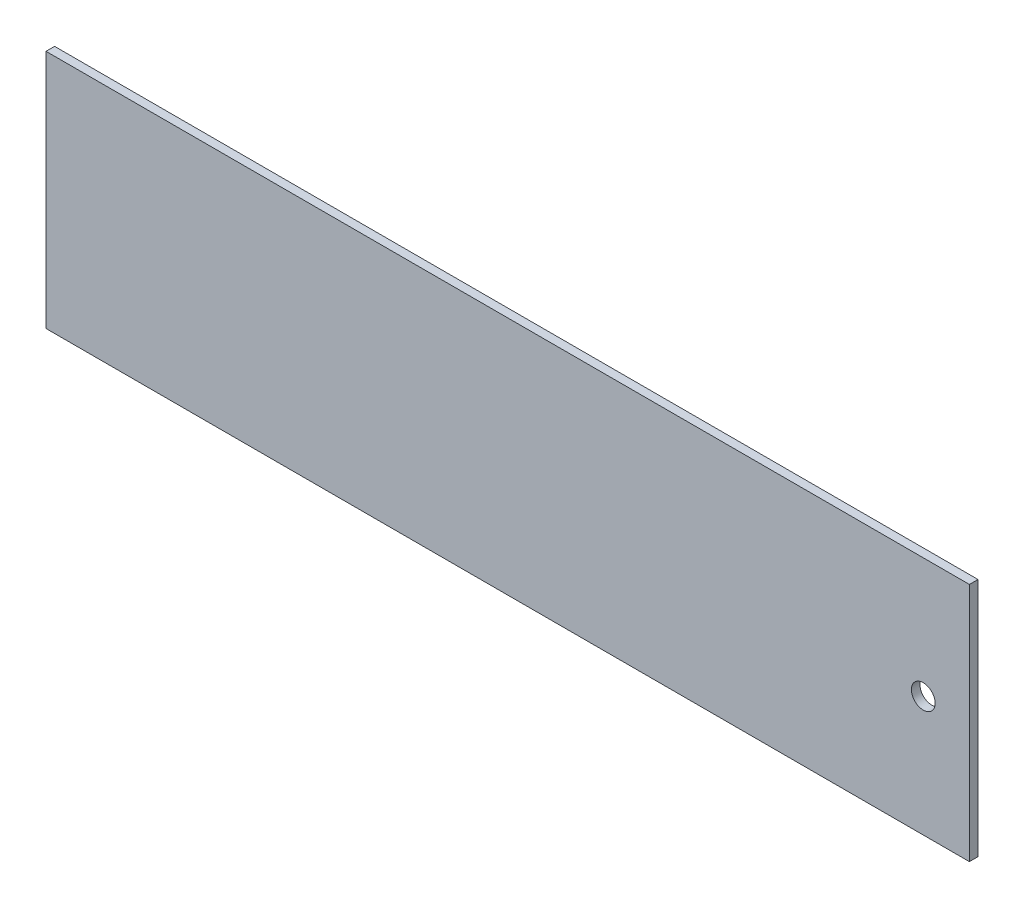
SolidWorks part; units mm, degrees
ref_plane "Front Plane" through (0, 0, 0) normal (0, 0, 1) x (1, 0, 0)
ref_plane "Top Plane" through (0, 0, 0) normal (0, 1, 0) x (1, 0, 0)
ref_plane "Right Plane" through (0, 0, 0) normal (1, 0, 0) x (0, 0, -1)
sketch "Sketch2" plane through (0, 0, 0) normal (0, 0, 1) x (1, 0, 0)
  line L1 (0, 0) -> (-254, 0)
  line L2 (0, 0) -> (0, 66.04)
  line L3 (0, 66.04) -> (-254, 66.04)
  line L4 (-254, 0) -> (-254, 66.04)
  dimension "D1" = 66.04
  dimension "D2" = 254
extrude "Boss-Extrude1" add sketch "Sketch2" along normal blind 2.3622
sketch "Sketch3" plane through (0, 0, 2.3622) normal (0, 0, 1) x (1, 0, 0)
  line L0 (0, 0) -> (0, 66.04) construction
  circle A0 centre (-12.7, 33.02) radius 3.2639
  point P2 (0, 33.02)
  point P3 (0, 0)
  dimension "D2" = 6.5278
  dimension "D1" = 12.7
extrude "Cut-Extrude1" cut sketch "Sketch3" against normal through all
